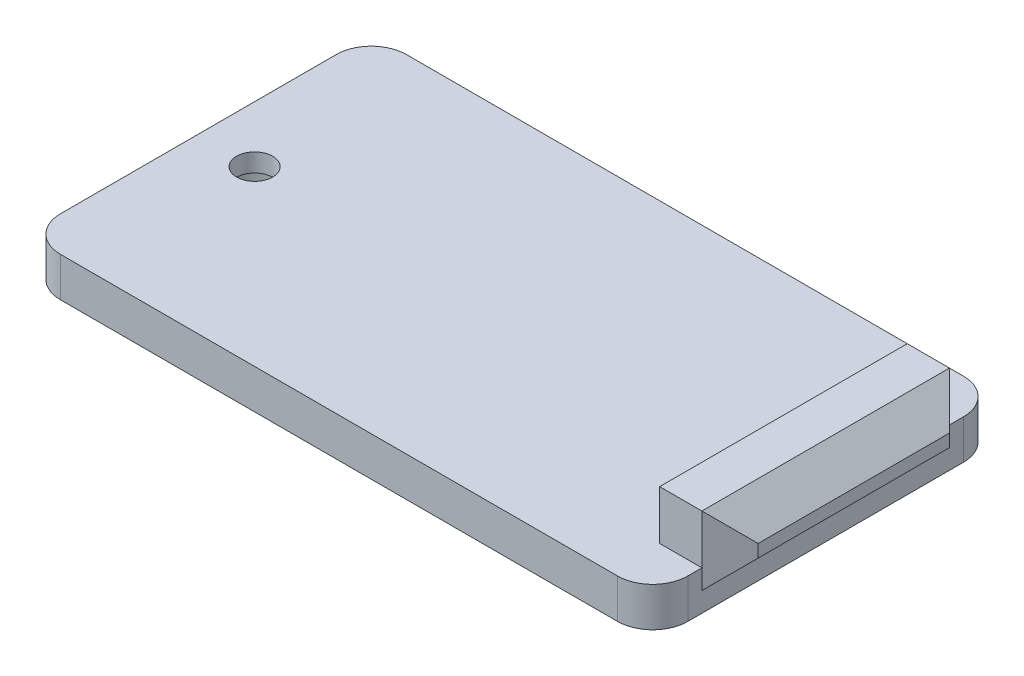
SolidWorks part; units mm, degrees
ref_plane "Front Plane" through (0, 0, 0) normal (0, 0, 1) x (1, 0, 0)
ref_plane "Top Plane" through (0, 0, 0) normal (0, 1, 0) x (1, 0, 0)
ref_plane "Right Plane" through (0, 0, 0) normal (1, 0, 0) x (0, 0, -1)
sketch "Sketch1" plane through (0, 0, 0) normal (0, 1, 0) x (1, 0, 0)
  line L0 (0, 15.621) -> (56.642, 15.621) construction
  line L1 (3.175, 0) -> (53.467, 0)
  line L2 (0, 3.175) -> (0, 28.067)
  line L3 (3.175, 31.242) -> (53.467, 31.242)
  line L4 (56.642, 3.175) -> (56.642, 28.067)
  arc A0 (3.175, 31.242) -> (0, 28.067) centre (3.175, 28.067) ccw
  arc A1 (56.642, 28.067) -> (53.467, 31.242) centre (53.467, 28.067) ccw
  arc A2 (53.467, 0) -> (56.642, 3.175) centre (53.467, 3.175) ccw
  arc A3 (0, 3.175) -> (3.175, 0) centre (3.175, 3.175) ccw
  circle A4 centre (5.08, 15.621) radius 1.632
  point P4 (0, 0)
  point P14 (55.7791, 2.381)
  dimension "D3" = 6.35
  dimension "D1" = 3.2639
  dimension "D2" = 5.08
  dimension "D4" = 3.175
  dimension "D5" = 3.175
  dimension "D6" = 50.292
  dimension "D7" = 24.892
extrude "Boss-Extrude1" add sketch "Sketch1" along normal blind 3.556
sketch "Sketch2" plane through (0, 0, 0) normal (0, -1, 0) x (1, 0, 0)
  circle A0 centre (5.08, -15.621) radius 3.175
  circle A1 centre (5.08, -15.621) radius 1.6319
  dimension "D1" = 6.35
extrude "Cut-Extrude1" cut sketch "Sketch2" against normal blind 1.905
sketch "Sketch3" plane through (56.642, 0, 0) normal (1, 0, 0) x (0, 0, -1)
  line L0 (3.175, 3.556) -> (3.175, 0) construction
  line L1 (4.445, 1.5875) -> (26.797, 1.5875)
  line L2 (4.445, 1.5875) -> (4.445, 8.1915)
  line L3 (4.445, 8.1915) -> (26.797, 8.1915)
  line L4 (26.797, 1.5875) -> (26.797, 8.1915)
  line L5 (28.067, 3.556) -> (28.067, 0) construction
  line L6 (3.175, 0) -> (28.067, 0) construction
  dimension "D1" = 1.27
  dimension "D2" = 1.27
  dimension "D3" = 1.5875
  dimension "D4" = 6.604
extrude "Boss-Extrude2" add sketch "Sketch3" along normal blind 2.54
chamfer "Chamfer1" distance 2.7305 angle 45 2 edges at (59.182, 1.5875, -15.621) (59.182, 8.1915, -15.621)
sketch "Sketch4" plane through (56.642, 0, 0) normal (-1, 0, 0) x (0, 0, 1)
  line L5 (-26.797, 8.001) -> (-4.445, 8.001)
  line L6 (-26.797, 8.001) -> (-26.797, 3.556)
  line L7 (-26.797, 3.556) -> (-4.445, 3.556)
  line L8 (-4.445, 8.001) -> (-4.445, 3.556)
extrude "Boss-Extrude3" add sketch "Sketch4" along normal blind 3.81
sketch "Sketch5" plane through (0, 0, 0) normal (0, -1, 0) x (1, 0, 0)
  line L0 (12.7, -9.9279) -> (12.7, -31.242) construction
  line L2 (53.467, -31.242) -> (3.175, -31.242) construction
  line L3 (0, -28.067) -> (0, -3.175) construction
  line L4 (0, -15.621) -> (56.642, -15.621) construction
  line L5 (56.642, -26.797) -> (56.642, -4.445) construction
  line L6 (11.1125, -9.271) -> (11.1141, -21.9)
  line L7 (14.2875, -9.271) -> (14.2859, -21.9)
  arc A0 (14.2875, -9.271) -> (11.1125, -9.271) centre (12.7, -9.271) ccw
  arc A1 (11.1141, -21.9) -> (14.2859, -21.9) centre (12.7, -21.971) ccw
  dimension "D2" = 3.175
  dimension "D3" = 3.175
  dimension "D1" = 12.7
  dimension "D4" = 12.7
  dimension "D5" = 6.35
extrude "Cut-Extrude2" cut sketch "Sketch5" against normal blind 1.778
sketch "Sketch6" plane through (0, 0, 0) normal (0, -1, 0) x (1, 0, 0)
  line L0 (14.2871, -12.5095) -> (56.642, -12.5095) construction
  line L1 (14.2859, -21.9) -> (14.2875, -9.271) construction
  line L2 (56.642, -26.797) -> (56.642, -4.445) construction
  line L3 (53.467, -31.242) -> (3.175, -31.242) construction
  text T0 "<b>PGM PIN</b>" font "Arial Rounded MT Bold" height 6.35
  dimension "D1" = 18.7325
extrude "Cut-Extrude3" cut sketch "Sketch6" against normal blind 1.016
chamfer "Chamfer2" distance 2.54 angle 45 2 edges at (59.182, 4.8895, -4.445) (59.182, 4.8895, -26.797)
